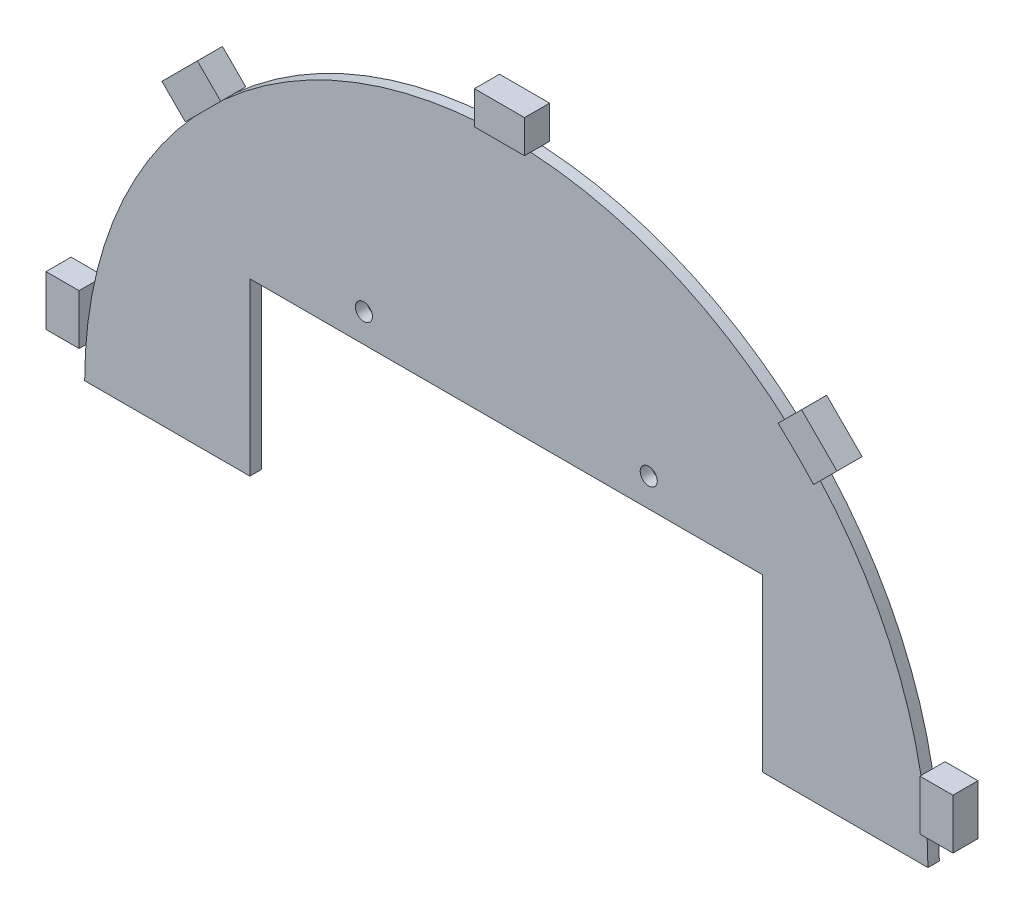
SolidWorks part; units mm, degrees
material "ABS"
ref_plane "Plan de face" through (0, 0, 0) normal (0, 0, 1) x (1, 0, 0)
ref_plane "Plan de dessus" through (0, 0, 0) normal (0, 1, 0) x (1, 0, 0)
ref_plane "Plan de droite" through (0, 0, 0) normal (1, 0, 0) x (0, 0, -1)
sketch "Esquisse3" plane through (0, 0, 0) normal (0, 0, 1) x (1, 0, 0)
  line L0 (-1000, 0) -> (49000, 0) construction
  line L1 (-74, 0) -> (-45, 0)
  line L2 (45, 0) -> (74, 0)
  line L3 (0, -1000) -> (0, 49000) construction
  line L4 (-45, 0) -> (-45, 30)
  line L5 (-45, 30) -> (45, 30)
  line L6 (45, 0) -> (45, 30)
  line L7 (-59.2426, 53.4899) -> (-55.1414, 49.3887)
  line L8 (-4.4, 79.8) -> (4.4, 79.8)
  line L9 (-4.4, 79.8) -> (-4.4, 74)
  line L10 (-4.4, 74) -> (4.4, 74)
  line L11 (4.4, 79.8) -> (4.4, 74)
  line L12 (-79.5878, 14.4) -> (-73.7878, 14.4)
  line L13 (-79.5878, 14.4) -> (-79.5878, 5.6)
  line L14 (-79.5878, 5.6) -> (-73.7878, 5.6)
  line L15 (-73.7878, 14.4) -> (-73.7878, 5.6)
  line L16 (79.5878, 14.4) -> (73.7878, 14.4)
  line L17 (79.5878, 14.4) -> (79.5878, 5.6)
  line L18 (79.5878, 5.6) -> (73.7878, 5.6)
  line L19 (73.7878, 14.4) -> (73.7878, 5.6)
  line L20 (-59.2426, 53.4899) -> (-53.0201, 59.7125)
  line L21 (-55.1414, 49.3887) -> (-48.9189, 55.6113)
  line L22 (-53.0201, 59.7125) -> (-48.9189, 55.6113)
  line L23 (53.02, 59.7125) -> (48.9188, 55.6113)
  line L24 (53.02, 59.7125) -> (59.2425, 53.4899)
  line L25 (48.9188, 55.6113) -> (55.1413, 49.3887)
  line L26 (59.2425, 53.4899) -> (55.1413, 49.3887)
  line L27 (-49.5076, 55) -> (-54.5527, 50)
  arc A0 (74, 0) -> (-74, 0) centre (0, 0) ccw
  circle A1 centre (-25, 35) radius 1.5
  circle A2 centre (25, 35) radius 1.5
  point P16 (-73.3212, 10)
  point P17 (73.3212, 10)
  point P26 (-79.5878, 10)
  point P27 (79.5878, 10)
  point P28 (-49.5076, 55)
  point P35 (-54.5527, 50)
  point P40 (-52.0302, 52.5)
  dimension "D22" = 3
  dimension "D1" = 148
  dimension "D2" = 29
  dimension "D3" = 29
  dimension "D4" = 30
  dimension "D5" = 5.8
  dimension "D6" = 8.8
  dimension "D7" = 4.4
  dimension "D8" = 10
  dimension "D9" = 10
  dimension "D10" = 5.8
  dimension "D11" = 5.8
  dimension "D12" = 8.8
  dimension "D13" = 8.8
  dimension "D14" = 5.8
  dimension "D15" = 5.8
  dimension "D16" = 8.8
  dimension "D17" = 8.8
  dimension "D18" = 45
  dimension "D19" = 50
  dimension "D20" = 55
  dimension "D21" = 53.02
  dimension "D23" = 20
  dimension "D24" = 5
extrude "Boss.-Extru.1" add sketch "Esquisse3" along normal blind 2 contours L2 A0 L25 L27 L21 L1 L4 L5 L6 A1 A2 region at (0.0002, 38.92, 0)
extrude "Boss.-Extru.6" add sketch "Esquisse3<3>" along normal blind 3.2 and the other way blind 1.2 contours L15 L12 L13 L14 | A0 L25 L26 L24 L23 | L16 L19 L18 L17 | L22 L21 L7 L20 | L8 L11 L10 L9 region at (-76.6878, 10, 0) region at (76.6878, 10, 0) region at (54.0952, 54.5689, 0)
sketch "Esquisse3<3>" plane through (0, 0, 0) normal (0, 0, 1) x (1, 0, 0) same geometry as "Esquisse3"
